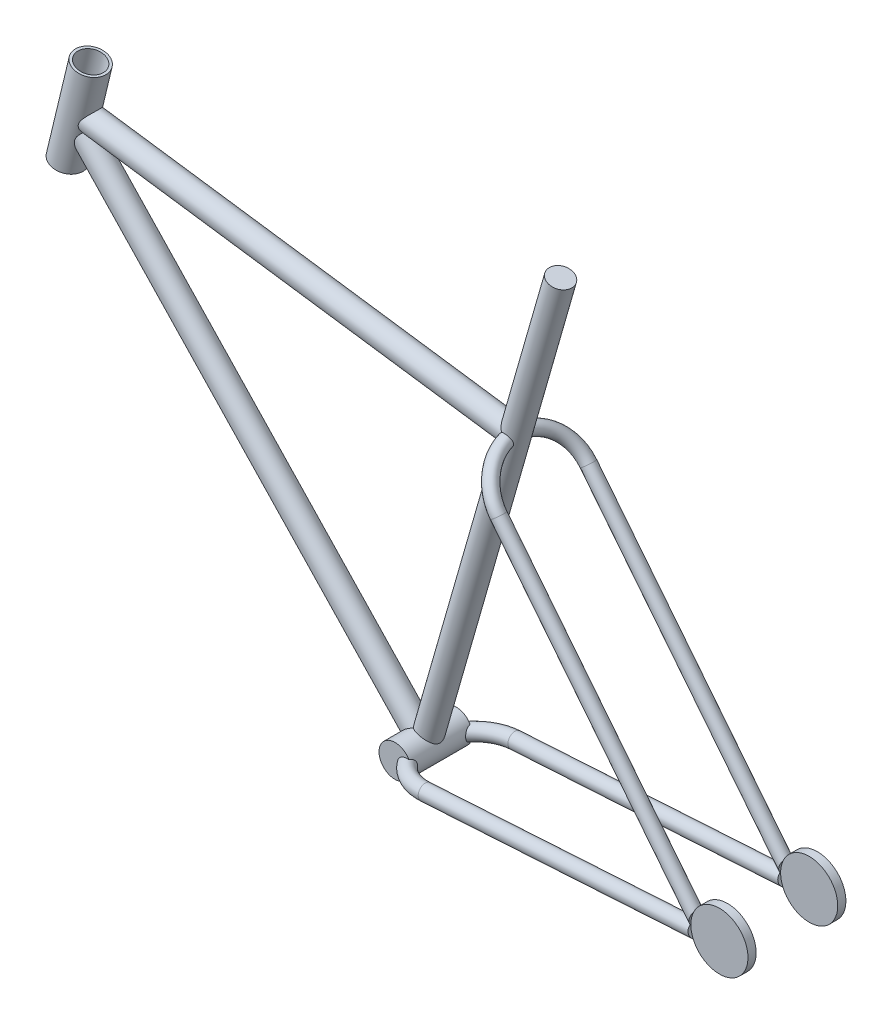
SolidWorks part; units mm, degrees
material "车架"
ref_plane "前视基准面" through (0, 0, 0) normal (0, 0, 1) x (1, 0, 0)
ref_plane "上视基准面" through (0, 0, 0) normal (0, 1, 0) x (1, 0, 0)
ref_plane "右视基准面" through (0, 0, 0) normal (1, 0, 0) x (0, 0, -1)
other "Configuration Table"
sketch "草图1" plane through (0, 0, 0) normal (0, 0, 1) x (1, 0, 0)
  circle A0 centre (0, 0) radius 19.65
  dimension "D1" = 39.3
extrude "凸台-拉伸1" add sketch "草图1" along normal mid plane 75
sketch "草图2" plane through (0, 0, 0) normal (0, 1, 0) x (1, 0, 0)
  line L0 (0, 37.5) -> (0, -37.5)
  line L1 (19.65, 37.5) -> (-19.65, 37.5) construction
  line L2 (-19.65, -37.5) -> (19.65, -37.5) construction
ref_plane "基准面1" through (0, 0, 0) normal (0.2756, 0.9613, 0) x (0, 0, 1)
sketch "草图3" plane through (0, 0, 0) normal (0.2756, 0.9613, 0) x (0, 0, 1)
  circle A0 centre (0, 0) radius 14.3
  dimension "D1" = 28.6
extrude "凸台-拉伸2" add sketch "草图3" along normal blind 400
ref_plane "基准面2" through (0, 0, 0) normal (-0.6884, 0.7254, 0) x (0, 0, 1)
sketch "草图4" plane through (0, 0, 0) normal (-0.6884, 0.7254, 0) x (0, 0, 1)
  circle A0 centre (0, 0) radius 14
  dimension "D1" = 28
extrude "凸台-拉伸3" add sketch "草图4" along normal blind 620
sketch "草图6" plane through (110.2549, 384.5047, 0) normal (0.2756, 0.9613, 0) x (0.9613, -0.2756, 0)
  line L0 (0, 14.3) -> (0, -14.3)
  line L1 (0, 37.5) -> (0, -37.5) construction
  circle A0 centre (0, 0) radius 14.3 construction
ref_plane "基准面3" through (55.1275, -7.7477, 0) normal (-0.9903, 0.1392, 0) x (0, 0, 1)
sketch "草图7" plane through (55.1275, -7.7477, 0) normal (-0.9903, 0.1392, 0) x (0, 0, 1)
  line L0 (-14.3, 396.1072) -> (14.3, 396.1072) construction
  circle A0 centre (0, 396.1072) radius 14
  dimension "D1" = 28
extrude "凸台-拉伸4" add sketch "草图7" along normal blind 540
sketch "草图8" plane through (110.2549, 384.5047, 0) normal (0.2756, 0.9613, 0) x (0.9613, -0.2756, 0)
  circle A0 centre (0, 0) radius 14.3
extrude "凸台-拉伸5" add sketch "草图8" along normal blind 200
sketch "草图9" plane through (-479.6173, 67.4058, 0) normal (-0.9903, 0.1392, 0) x (0, 0, 1)
  line L0 (14, 396.1072) -> (-14, 396.1072)
  arc A0 (10.6952, 387.0733) -> (-10.6952, 387.0733) centre (0, 396.1072) ccw construction
ref_plane "基准面4" through (81.2069, 338.2511, 0) normal (0.2334, 0.9724, 0) x (0, 0, -1)
sketch "草图10" plane through (81.2069, 338.2511, 0) normal (0.2334, 0.9724, 0) x (0, 0, -1)
  line L0 (-14, 520.0662) -> (14, 520.0662) construction
  circle A0 centre (0, 520.0662) radius 19.1
  dimension "D1" = 38.2
extrude "凸台-拉伸6" add sketch "草图10" along normal mid plane 120
sketch "草图11" plane through (0, 0, 0) normal (0, 0, 1) x (1, 0, 0)
  line L0 (0, 0) -> (300, 18.3488)
  line L1 (0, 0) -> (400, 0)
  line L2 (-400.25, 442.1139) -> (92.0581, 372.9245) construction
  line L3 (99.8518, 400.1043) -> (-402.2049, 470.6638) construction
  line L4 (17.4608, 9.0134) -> (179.1285, 572.8154) construction
  line L5 (151.6364, 580.6986) -> (99.8518, 400.1043) construction
  line L6 (-400.25, 442.1139) -> (92.0581, 372.9245)
  line L7 (99.8518, 400.1043) -> (-402.2049, 470.6638)
  line L8 (17.4608, 9.0134) -> (179.1285, 572.8154)
  line L9 (151.6364, 580.6986) -> (99.8518, 400.1043)
  line L10 (110.2549, 384.5047) -> (402.8368, 16.6788)
  line L11 (95.9549, 386.5144) -> (124.5549, 382.4949)
  dimension "D1" = 300
  dimension "D2" = 400
  dimension "D3" = 3.5
  dimension "D4" = 14
  dimension "D5" = 51.5
  dimension "D6" = 470
ref_plane "基准面5" through (0, 0, 0) normal (0.061, -0.9981, 0) x (0.9981, 0.061, 0)
sketch "草图12" plane through (0, 0, 0) normal (0.061, -0.9981, 0) x (0.9981, 0.061, 0)
  line L0 (400, 55) -> (55, 55)
  line L1 (0, 0) -> (300.5606, 0) construction
  arc A0 (0, 0) -> (55, 55) centre (55, 0) cw
  dimension "D1" = 55
  dimension "D2" = 400
  dimension "D3" = 55
ref_plane "基准面6" through (399.2539, 24.4194, 55) normal (-0.9981, -0.061, 0) x (0, 0, 1)
sketch "草图13" plane through (399.2539, 24.4194, 55) normal (-0.9981, -0.061, 0) x (0, 0, 1)
  line L0 (-55, 0) -> (0, 0) construction
  circle A0 centre (0, 0) radius 9
  dimension "D1" = 18
sweep "扫描1" add profiles "草图13" path "草图12"
mirror "镜向1" about plane through (0, 0, 0) normal (0, 0, 1) of "扫描1"
ref_plane "基准面8" through (254.8534, 202.7195, 0) normal (-0.7826, -0.6225, 0) x (0.6225, -0.7826, 0)
sketch "草图16" plane through (254.8534, 202.7195, 0) normal (-0.7826, -0.6225, 0) x (0.6225, -0.7826, 0)
  line L0 (-232.2812, -14.3) -> (-232.2812, 14.3) construction
  line L1 (-232.2812, -14.3) -> (-232.2812, 14.3)
  line L2 (222.7188, 55) -> (-177.2812, 55)
  line L3 (0, 0) -> (249.0059, 0) construction
  line L4 (0, 0) -> (249.0059, 0)
  line L5 (-232.2812, 0) -> (237.7188, 0) construction
  arc A0 (-232.2812, 0) -> (-177.2812, 55) centre (-177.2812, 0) cw
  dimension "D1" = 55
  dimension "D2" = 55
  dimension "D3" = 400
ref_plane "基准面9" through (393.4991, 28.418, 55) normal (-0.6225, 0.7826, 0) x (0.7826, 0.6225, 0)
sketch "草图17" plane through (393.4991, 28.418, 55) normal (-0.6225, 0.7826, 0) x (0.7826, 0.6225, 0)
  circle A0 centre (0, 0) radius 8
  dimension "D1" = 16
sweep "扫描2" add profiles "草图17" path "草图16"
mirror "镜向2" about plane through (0, 0, 0) normal (0, 0, 1) of "扫描2"
sketch "草图18" plane through (95.2136, 396.5933, 0) normal (0.2334, 0.9724, 0) x (0.9724, -0.2334, 0)
  line L0 (-520.0662, -14) -> (-520.0662, 14) construction
  circle A0 centre (-520.0662, 0) radius 16
  dimension "D1" = 32
extrude "切除-拉伸1" cut sketch "草图18" against normal up to next
ref_plane "基准面10" through (0, 0, 50) normal (0, 0, 1) x (1, 0, 0)
sketch "草图19" plane through (0, 0, 50) normal (0, 0, 1) x (1, 0, 0)
  circle A0 centre (420, 30) radius 35
  dimension "D3" = 70
  dimension "D1" = 420
  dimension "D2" = 30
extrude "凸台-拉伸7" add sketch "草图19" along normal blind 10
sketch "草图20" plane through (0, 0, 50) normal (0, 0, -1) x (-1, 0, 0)
  arc A0 (-388.3443, 44.9304) -> (-387.8255, 16.2231) centre (-420, 30) ccw construction
  circle A1 centre (-420, 30) radius 35
extrude "切除-拉伸2" cut sketch "草图20" along normal up to next
mirror "镜向4" about plane through (0, 0, 0) normal (0, 0, 1) of "凸台-拉伸7"
mirror "镜向6" about plane through (0, 0, 0) normal (0, 0, 1) of "切除-拉伸2"
sketch "草图21" plane through (0, 0, -60) normal (0, 0, -1) x (-1, 0, 0)
  arc A0 (-388.3443, 44.9304) -> (-387.8255, 16.2231) centre (-420, 30) ccw construction
  circle A1 centre (-420, 30) radius 35
extrude "切除-拉伸3" cut sketch "草图21" along normal up to next
mirror "镜向7" about plane through (0, 0, 0) normal (0, 0, 1) of "切除-拉伸3"
